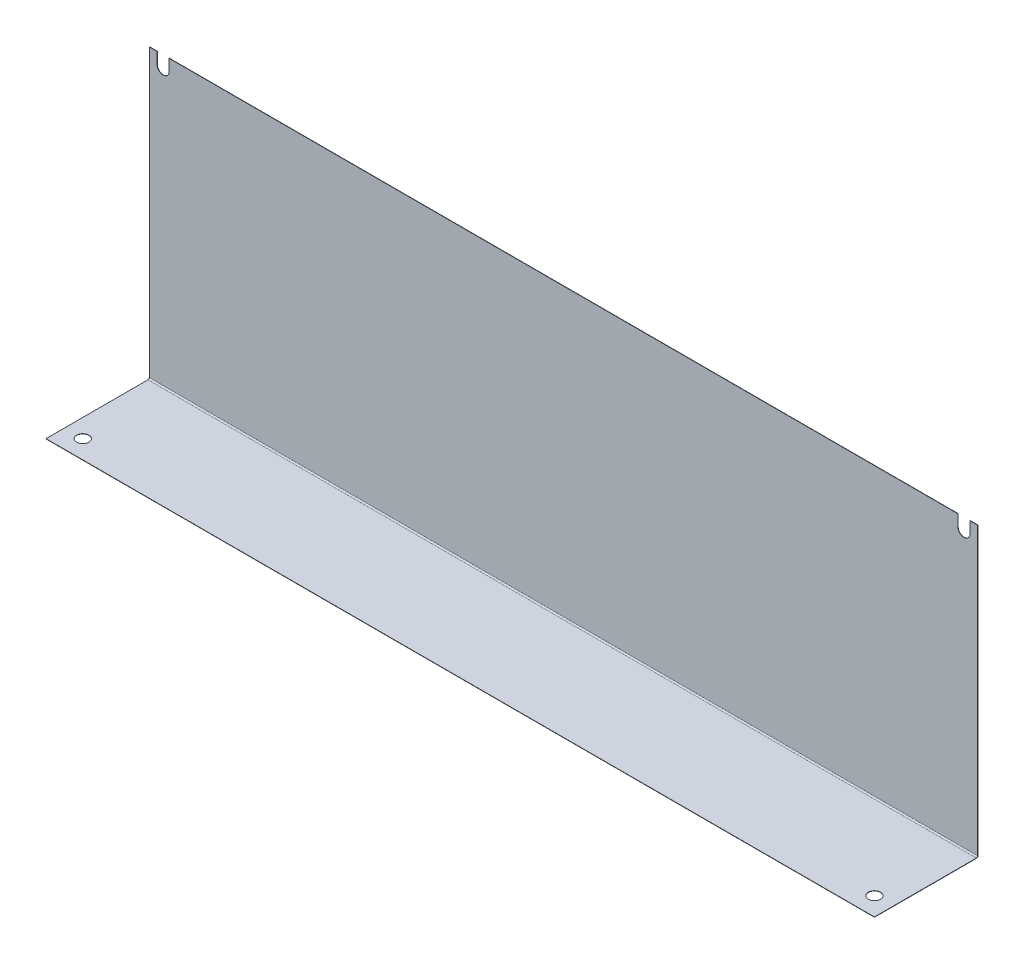
SolidWorks part; units mm, degrees
note: The reader was unsure of these and kept them because the rebuilt part matched: thickness of "Base-Flange1", "Edge-Flange1", "Sheet-Metal(1)", "Sheet-Metal(2)", "Sheet-Metal(3)", "Sheet-Metal(6)"; flange length of "Edge-Flange1".
ref_plane "Front Plane" through (0, 0, 0) normal (0, 0, 1) x (1, 0, 0)
ref_plane "Top Plane" through (0, 0, 0) normal (0, 1, 0) x (1, 0, 0)
ref_plane "Right Plane" through (0, 0, 0) normal (1, 0, 0) x (0, 0, -1)
sketch "Sketch1" plane through (0, 0, 0) normal (0, 1, 0) x (1, 0, 0)
  line L1 (0, 0) -> (457.2, 0)
  line L2 (0, 0) -> (0, 57.15)
  line L3 (0, 57.15) -> (457.2, 57.15)
  line L4 (457.2, 0) -> (457.2, 57.15)
  dimension "D1" = 457.2
  dimension "D2" = 57.15
base flange "Base-Flange1" sketch "Sketch1" thickness 0.1588 reverse thickness direction no parameters "D1"=0.7366
edge flange "Edge-Flange1" sketch "Sketch8" flange angle 90 flange length 158.75 flange position material inside bend radius 0.7366 thickness 0.1588 relief rectangular parameters "D6"=10
sketch "Sketch8" plane through (0, 0, -57.15) normal (0, 0, -1) x (-1, 0, 0)
  line L0 (-457.2, 0) -> (0, 0) construction
  line L1 (-457.2, 0) -> (0, 0)
  line L2 (-457.2, 0) -> (-457.2, 158.75)
  line L3 (-457.2, 158.75) -> (0, 158.75)
  line L4 (0, 158.75) -> (0, 0)
  dimension "D1" = 158.75
bend "EdgeBend1" bend radius 0.7366 bend angle 90 parameters "D5"=1
sketch "Sketch9" plane through (0, 0, -57.15) normal (0, 0, -1) x (-1, 0, 0)
  line L0 (-446.278, 152.4) -> (-446.278, 158.75)
  line L1 (0, 158.75) -> (-457.2, 158.75) construction
  line L2 (-452.882, 152.4) -> (-452.882, 158.75)
  line L4 (-457.2, 158.75) -> (-457.2, 0.7366) construction
  line L5 (-452.882, 158.75) -> (-446.278, 158.75)
  line L6 (-10.922, 152.4) -> (-10.922, 158.75)
  line L7 (-10.922, 158.75) -> (-4.318, 158.75)
  line L8 (-4.318, 158.75) -> (-4.318, 152.4)
  line L9 (0, 0.7366) -> (0, 158.75) construction
  arc A0 (-452.882, 152.4) -> (-446.278, 152.4) centre (-449.58, 152.4) ccw
  arc A1 (-10.922, 152.4) -> (-4.318, 152.4) centre (-7.62, 152.4) ccw
  dimension "D1" = 6.604
  dimension "D4" = 6.604
  dimension "D2" = 6.35
  dimension "D3" = 7.62
  dimension "D5" = 6.35
  dimension "D6" = 7.62
extrude "Cut-Extrude1" cut sketch "Sketch9" against normal through all normal cut yes
hole_wizard "1/4 Clearance Hole2" positions "3DSketch3" profile "Sketch13" hole size "1/4" standard "ANSI Inch"
sketch3d "3DSketch3"
  line L0 (0, -0.1587, -56.2547) -> (0, -0.1588, 0) construction
  line L1 (0, -0.1588, 0) -> (457.2, -0.1588, 0) construction
  line L2 (457.2, -0.1588, 0) -> (457.2, -0.1588, -56.2547) construction
  point P0 (10.16, -0.1588, -10.16)
  point P2 (447.04, -0.1588, -10.16)
  point P17 (266.1765, 0, 40.0596)
  dimension "D1" = 10.16
  dimension "D2" = 10.16
  dimension "D3" = 10.16
  dimension "D5" = 10.16
sketch "Sketch13" plane through (10.16, -0.1588, -10.16) normal (1, 0, 0) x (0, 0, -1)
  line L0 (0, 0) -> (0, 27.4298)
  line L1 (0, 27.4298) -> (3.3782, 25.4)
  line L2 (3.3782, 25.4) -> (3.3782, 0)
  line L5 (3.3782, 0) -> (0, 0)
  line L10 (0, 27.4298) -> (-3.3782, 25.4) construction
  line L11 (0, -6.35) -> (0, 107.95) construction
  dimension "Hole Dia." = 6.7564
  dimension "Hole Depth" = 25.4
  dimension "Drill Angle" = 118
sketch "Bend-Lines1" plane through (0, 0, 0) normal (0, 1, 0) x (1, 0, 0)
sketch "Bounding-Box1" plane through (0, 0, 0) normal (0, 1, 0) x (1, 0, 0)
sheet metal parameters "Sheet-Metal(1)" thickness 0.1588 parameters "D1"=0.7366
flat pattern "Flat-Pattern(1)" [suppressed]
sketch "Bend-Lines2" plane through (0, 0, 0) normal (0, 1, 0) x (1, 0, 0)
sketch "Bounding-Box2" [suppressed] plane through (0, 0, 0) normal (0, 1, 0) x (1, 0, 0)
sheet metal parameters "Sheet-Metal(2)" thickness 0.1588 parameters "D1"=0.7366, "D7"=3.175
flat pattern "Flat-Pattern(1)" [suppressed]
sketch "Bend-Lines2" plane through (0, 0, 0) normal (0, 1, 0) x (1, 0, 0)
sketch "Bounding-Box2" [suppressed] plane through (0, 0, 0) normal (0, 1, 0) x (1, 0, 0)
bend of the flat pattern "Flatten-<EdgeBend1>1"
sheet metal parameters "Sheet-Metal(3)" thickness 0.1588 parameters "D1"=0.7366, "D7"=3.175
flat pattern "Flat-Pattern(1)" [suppressed]
sketch "Bend-Lines2" plane through (0, 0, 0) normal (0, 1, 0) x (1, 0, 0)
sketch "Bounding-Box2" [suppressed] plane through (0, 0, 0) normal (0, 1, 0) x (1, 0, 0)
bend of the flat pattern "Flatten-<EdgeBend1>1"
sheet metal parameters "Sheet-Metal(6)" thickness 0.1588 parameters "D1"=0.7366, "D7"=3.175
flat pattern "Flat-Pattern(1)" [suppressed]
sketch "Bend-Lines2" plane through (0, 0, 0) normal (0, 1, 0) x (1, 0, 0)
sketch "Bounding-Box2" [suppressed] plane through (0, 0, 0) normal (0, 1, 0) x (1, 0, 0)
bend of the flat pattern "Flatten-<EdgeBend1>1"
